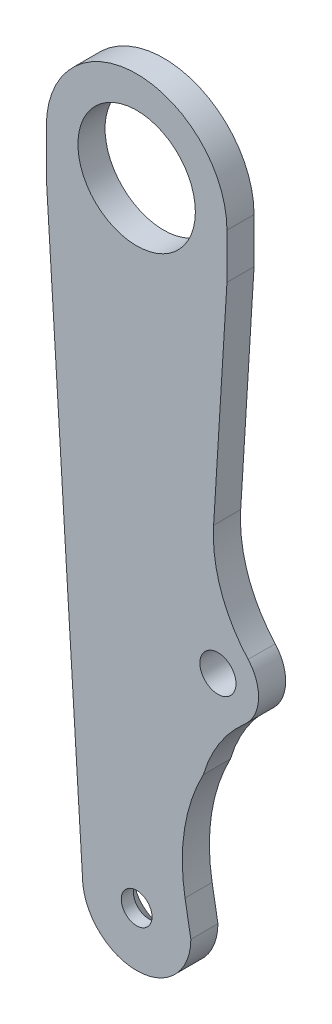
SolidWorks part; units mm, degrees
material "Thornel Mat VMA"
ref_plane "前视基准面" through (0, 0, 0) normal (0, 0, 1) x (1, 0, 0)
ref_plane "上视基准面" through (0, 0, 0) normal (0, 1, 0) x (1, 0, 0)
ref_plane "右视基准面" through (0, 0, 0) normal (1, 0, 0) x (0, 0, -1)
sketch "草图1" plane through (0, 0, 0) normal (0, 0, 1) x (1, 0, 0)
  line L1 (-10, 35) -> (10, 35)
  line L2 (-10, 35) -> (-10, -35)
  line L3 (-10, -35) -> (10, -35)
  line L4 (10, 35) -> (10, -35)
  line L5 (-10, 35) -> (10, -35) construction
  line L6 (-10, -35) -> (10, 35) construction
  circle A0 centre (0, 35) radius 10
  point P0 (0, 0)
  dimension "D2" = 70
  dimension "D1" = 20
extrude "凸台-拉伸1" add sketch "草图1" along normal blind 3 contours L1 A0 | A0 L2 L3 L4 | L1 A0
sketch "草图2" plane through (0, 0, 3) normal (0, 0, 1) x (1, 0, 0)
  line L0 (-10, 35) -> (10, 35) construction
  line L1 (10, 35) -> (10, -35) construction
  arc A0 (10, 35) -> (-10, 35) centre (0, 35) ccw construction
  circle A1 centre (0, 35) radius 6.5
  dimension "D1" = 13
extrude "切除-拉伸1" cut sketch "草图2" against normal through all
sketch "草图4" plane through (0, 0, 0) normal (0, 0, -1) x (-1, 0, 0)
  line L1 (6, -35) -> (10, -35)
  line L2 (10, -35) -> (-10, -35) construction
  line L3 (10, -35) -> (10, 30)
  line L4 (10, 35) -> (10, -35) construction
  line L5 (10, 30) -> (6, -35)
  line L6 (0, -35) -> (0, 45) construction
  line L7 (-10, 30) -> (-6, -35)
  line L8 (-10, -35) -> (-10, 30)
  line L9 (-6, -35) -> (-10, -35)
  arc A1 (10, 35) -> (-10, 35) centre (0, 35) ccw construction
  circle A2 centre (0, -35) radius 6
  line M13 (-10, 35) -> (-10, -35)
  line M14 (-10, -35) -> (10, -35)
  line M15 (10, -35) -> (10, 35)
  dimension "D1" = 12
  dimension "D2" = 65
extrude "切除-拉伸3" cut sketch "草图4" against normal blind 3.5 contours L5 M15 M14 | L7 M13 M14 region at (-8.6667, -13.3333, 0) region at (8.6667, -13.3333, 0)
extrude "凸台-拉伸3" add sketch "草图4<3>" against normal up to surface (3 mm away) contours A2 up to face at (0, 11.6667, 3)
sketch "草图4<3>" plane through (0, 0, 0) normal (0, 0, -1) x (-1, 0, 0) same geometry as "草图4"
sketch "草图5" plane through (0, 0, 0) normal (0, 0, -1) x (-1, 0, 0)
  circle A0 centre (0, -35) radius 1.5
  dimension "D1" = 3
extrude "切除-拉伸4" cut sketch "草图5" against normal through all
sketch "草图6" plane through (0, 0, 0) normal (0, 0, -1) x (-1, 0, 0)
  line L0 (0, 35) -> (-9, 35) construction
  line L1 (-9, 35) -> (-9, -8) construction
  circle A0 centre (-9, -8) radius 4.5
  dimension "D1" = 9
  dimension "D3" = 9
  dimension "D2" = 43
extrude "凸台-拉伸4" add sketch "草图6" against normal up to surface (3 mm away) up to face at (-1.5, -35, 3)
fillet "圆角1" radius 15 2 edges at (7.9305, -3.6289, 1.5) (7.4026, -12.207, 1.5)
sketch "草图8" plane through (0, 0, 3) normal (0, 0, 1) x (1, 0, 0)
  circle A0 centre (9, -8) radius 2
  dimension "D1" = 4
extrude "切除-拉伸5" cut sketch "草图8" against normal through all
sketch "草图11" plane through (0, 0, 3) normal (0, 0, 1) x (1, 0, 0)
  line L0 (6, -35) -> (3.0906, -18.5)
  line L1 (3.0906, -18.5) -> (7.3911, -18.5)
  line L2 (6, -35) -> (6.8121, -21.8037) construction
  line L3 (6, -35) -> (6.8121, -21.8037)
  arc A0 (11.9501, -11.3981) -> (6.8121, -21.8037) centre (21.7838, -22.725) ccw construction
  arc A1 (11.9501, -11.3981) -> (6.8121, -21.8037) centre (21.7838, -22.725) ccw
  line M4 (6, -35) -> (6.8121, -21.8037)
  arc M5 (6.8121, -21.8037) -> (11.9501, -11.3981) centre (21.7838, -22.725) cw
  dimension "D1" = 80
  dimension "D2" = 16.5
extrude "切除-拉伸9" cut sketch "草图11" against normal through all contours L1 L0 M4 M5 region at (5.39, -23.9415, 3)
fillet "圆角3" radius 20 1 edges at (3.0906, -18.5, 1.5)
hole_wizard "M3 六角凹锥坑螺钉的锥形沉头孔2" positions "3D草图3" profile "草图14" countersink size "M3" standard "ISO" end condition through all
sketch3d "3D草图3"
  line L0 (0, -35, 3) -> (0, -35, 0) construction
  point P0 (0, -35, 0)
sketch "草图14" plane through (0, -35, 0) normal (1, 0, 0) x (0, 1, 0)
  line L0 (0, 0) -> (0, 3)
  line L1 (0, 3) -> (1.7, 3)
  line L2 (1.7, 3) -> (1.7, 1.66)
  line L3 (1.7, 1.66) -> (3.36, 0)
  line L5 (3.36, 0) -> (0, 0)
  line L6 (-1.7, 1.66) -> (-3.36, 0) construction
  line L11 (0, -6.35) -> (0, 107.95) construction
  dimension "通孔孔直径" = 3.4
  dimension "通孔孔深度" = 3
  dimension "近端锥形沉头孔直径" = 6.72
  dimension "近端锥形沉头孔角度" = 90
